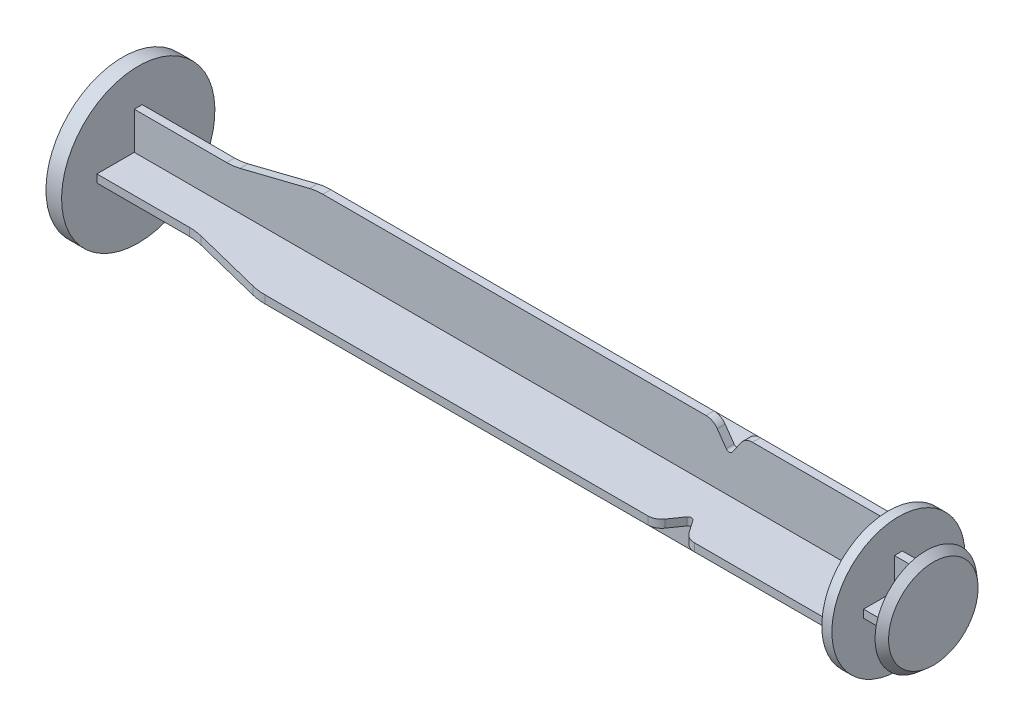
SolidWorks part; units mm, degrees
ref_plane "Front" through (0, 0, 0) normal (0, 0, 1) x (1, 0, 0)
ref_plane "Top" through (0, 0, 0) normal (0, 1, 0) x (1, 0, 0)
ref_plane "Right" through (0, 0, 0) normal (1, 0, 0) x (0, 0, -1)
sketch "Sketch1" plane through (0, 0, 0) normal (0, 0, 1) x (1, 0, 0)
  line L0 (0, 0) -> (84.5, 0)
  line L1 (84.5, 0) -> (84.5, 6.75)
  line L2 (84.5, 6.75) -> (68.25, 6.75)
  line L3 (68.25, 6.75) -> (66.5, 4.25)
  line L4 (66.5, 4.25) -> (64.75, 6.75)
  line L5 (64.75, 6.75) -> (21.5, 6.75)
  line L6 (21.5, 6.75) -> (12.5, 4.5)
  line L7 (12.5, 4.5) -> (0, 4.5)
  line L8 (0, 4.5) -> (0, 0)
  line L9 (66.5, 4.25) -> (66.5, 6.75) construction
  line L10 (66.5, 6.75) -> (68.25, 6.75) construction
  dimension "D1" = 84.5
  dimension "D2" = 2.5
  dimension "D3" = 18
  dimension "D4" = 63
  dimension "D5" = 12.5
  dimension "D6" = 6.75
  dimension "D7" = 3.5
  dimension "D8" = 4.5
extrude "Boss-Extrude1" add sketch "Sketch1" along normal blind 0.43 and the other way blind 0.43
sketch "Sketch2" plane through (0, 0, 0) normal (-1, 0, 0) x (0, 0, 1)
  circle A0 centre (0, 0) radius 8.35
  dimension "D1" = 16.7
extrude "Boss-Extrude2" add sketch "Sketch2" against normal blind 1.7
ref_axis "Axis1" through (1.7, 0, 0) along (1, 0, 0)
pattern_circular "CirPattern1" count 4 over 360 about axis through (1.7, 0, 0) along (1, 0, 0) of "Boss-Extrude1"
sketch "Sketch3" plane through (84.5, 0, 0) normal (1, 0, 0) x (0, 0, -1)
  circle A0 centre (0, 0) radius 7.25
  dimension "D1" = 14.5
extrude "Boss-Extrude3" add sketch "Sketch3" against normal blind 1.1
sketch "Sketch4" plane through (84.5, 0, 0) normal (1, 0, 0) x (0, 0, -1)
  line L0 (0, 0) -> (0, 3.8) construction
  line L1 (0, 0) -> (-3.8, 0) construction
  line L2 (0, 0) -> (0, -3.8) construction
  line L3 (0, 0) -> (3.8, 0) construction
  line L4 (-3.8, -0.43) -> (-3.8, 0.43)
  line L5 (0.43, 3.8) -> (-0.43, 3.8)
  line L6 (0.43, -3.8) -> (-0.43, -3.8)
  line L7 (3.8, -0.43) -> (3.8, 0.43)
  line L8 (-0.43, 3.8) -> (-0.43, 0.43)
  line L9 (-0.43, 0.43) -> (-3.8, 0.43)
  line L10 (-3.8, -0.43) -> (-0.43, -0.43)
  line L11 (-0.43, -0.43) -> (-0.43, -3.8)
  line L12 (0.43, -3.8) -> (0.43, -0.43)
  line L13 (0.43, -0.43) -> (3.8, -0.43)
  line L14 (3.8, 0.43) -> (0.43, 0.43)
  line L15 (0.43, 0.43) -> (0.43, 3.8)
  point P9 (-3.8, 0)
  point P12 (0, 3.8)
  point P15 (0, -3.8)
  point P18 (3.8, 0)
  dimension "D1" = 0.86
  dimension "D2" = 7.6
extrude "Boss-Extrude4" add sketch "Sketch4" along normal blind 3
sketch "Sketch6" plane through (0, 0, 0) normal (0, 1, 0) x (1, 0, 0)
  line L0 (87.5, 0) -> (88.3, 0)
  line L1 (87.5, -0.43) -> (87.5, 0.43) construction
  line L2 (88.3, 0) -> (88.3, -4.875)
  line L3 (88.3, -4.875) -> (87.5, -5.55)
  line L4 (87.5, -5.55) -> (87.5, 0)
  dimension "D1" = 5.55
  dimension "D2" = 4.875
  dimension "D3" = 0.8
revolve "Revolve1" add sketch "Sketch6" angle 360 about L0
fillet "Fillet1" radius 0.4 4 edges at (66.5, 0, -4.25) (66.5, -4.25, 0) (66.5, 0, 4.25) (66.5, 4.25, 0)
fillet "Fillet2" radius 1.5 8 edges at (68.25, 0, -6.75) (64.75, 0, -6.75) (68.25, 6.75, 0) (64.75, 6.75, 0) (64.75, 0, 6.75) (68.25, 0, 6.75) (64.75, -6.75, 0) (68.25, -6.75, 0)
fillet "Fillet3" radius 6 8 edges at (12.5, 4.5, 0) (21.5, 6.75, 0) (12.5, 0, -4.5) (21.5, 0, -6.75) (21.5, -6.75, 0) (12.5, -4.5, 0) (12.5, 0, 4.5) (21.5, 0, 6.75)
